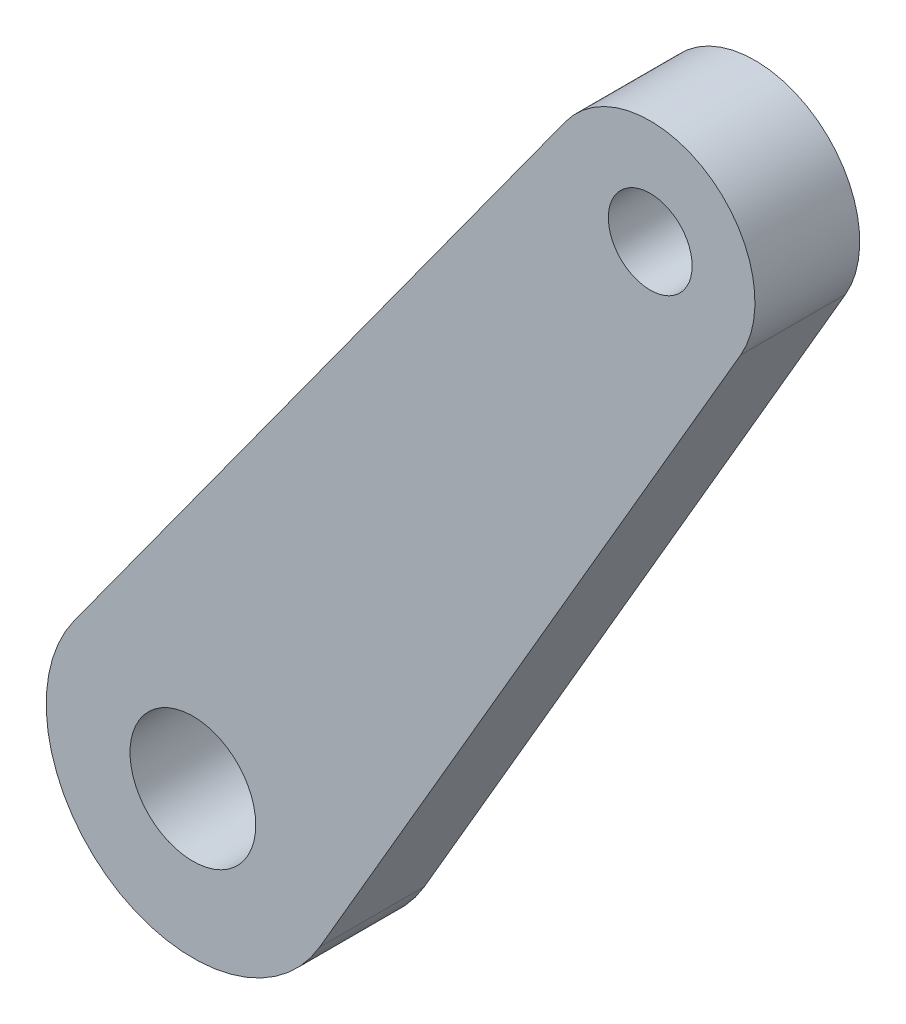
SolidWorks part; units mm, degrees
ref_plane "Front Plane" through (0, 0, 0) normal (0, 0, 1) x (1, 0, 0)
ref_plane "Top Plane" through (0, 0, 0) normal (0, 1, 0) x (1, 0, 0)
ref_plane "Right Plane" through (0, 0, 0) normal (1, 0, 0) x (0, 0, -1)
sketch "Sketch1" plane through (0, 0, 0) normal (0, 0, 1) x (1, 0, 0)
  line L0 (-65.6677, 14.1081) -> (-42.2221, 46.4547)
  line L1 (-33.8525, 41.0049) -> (-53.9503, 6.4785)
  circle A0 centre (-60, 10) radius 3 construction
  circle A1 centre (-38.1737, 43.5203) radius 2 construction
  circle A2 centre (-60, 10) radius 3
  circle A3 centre (-38.1737, 43.5203) radius 2
  arc A4 (-42.2221, 46.4547) -> (-33.8525, 41.0049) centre (-38.1737, 43.5203) cw
  arc A5 (-53.9503, 6.4785) -> (-65.6677, 14.1081) centre (-60, 10) cw
  point P2 (0, 0)
  point P11 (0, 0)
  dimension "D1" = 5
  dimension "D2" = 7
extrude "Boss-Extrude1" add sketch "Sketch1" along normal blind 5 from offset 10
